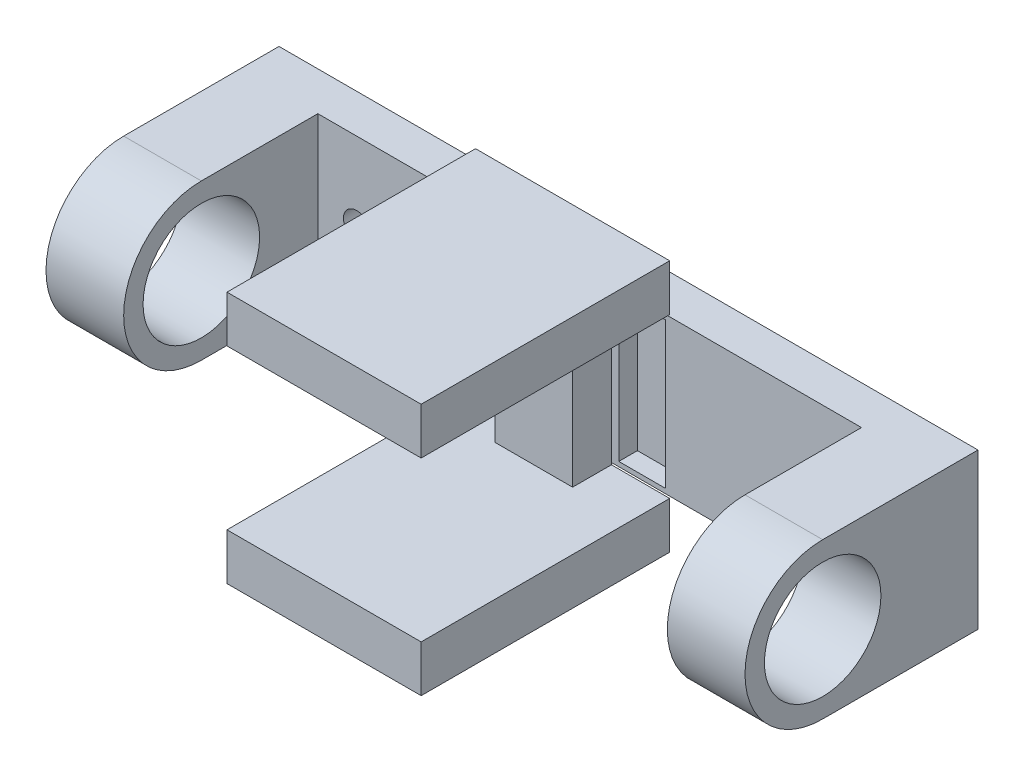
SolidWorks part; units mm, degrees
ref_plane "Plan de face" through (0, 0, 0) normal (0, 0, 1) x (1, 0, 0)
ref_plane "Plan de dessus" through (0, 0, 0) normal (0, 1, 0) x (1, 0, 0)
ref_plane "Plan de droite" through (0, 0, 0) normal (1, 0, 0) x (0, 0, -1)
sketch "Esquisse1" plane through (0, 0, 0) normal (0, 0, 1) x (1, 0, 0)
  line L1 (0, 0) -> (90, 0)
  line L2 (0, 0) -> (0, 20)
  line L3 (0, 20) -> (90, 20)
  line L4 (90, 0) -> (90, 20)
  dimension "D1" = 90
  dimension "D2" = 20
extrude "Boss.-Extru.1" add sketch "Esquisse1" along normal blind 5
sketch "Esquisse2" plane through (0, 0, 5) normal (0, 0, 1) x (1, 0, 0)
  line L0 (90, 20) -> (0, 20) construction
  line L1 (0, 0) -> (10, 0)
  line L2 (0, 0) -> (0, 20)
  line L3 (0, 20) -> (10, 20)
  line L4 (10, 0) -> (10, 20)
  dimension "D1" = 10
extrude "Boss.-Extru.2" add sketch "Esquisse2" along normal blind 30
sketch "Esquisse3" plane through (0, 0, 0) normal (-1, 0, 0) x (0, 0, 1)
  line L0 (0, 20) -> (0, 0) construction
  line L1 (35, 20) -> (0, 20) construction
  line L2 (35, 20) -> (35, 0) construction
  line L3 (35, 0) -> (0, 0) construction
  line L4 (35, 20) -> (20, 20)
  line L5 (35, 20) -> (35, 0)
  line L6 (35, 0) -> (20, 0)
  circle A0 centre (20, 10) radius 7.5
  arc A1 (20, 0) -> (20, 20) centre (20, 10) ccw
  dimension "D2" = 15
  dimension "D4" = 20
  dimension "D1" = 20
  dimension "D3" = 10
extrude "Enlèv. mat.-Extru.1" cut sketch "Esquisse3" against normal up to surface (10 mm away) up to face at (10, 10, 20)
ref_plane "Plan1" through (45, 0, 0) normal (1, 0, 0) x (0, 0, -1)
mirror "Symétrie1" about plane through (45, 0, 0) normal (1, 0, 0) of "Enlèv. mat.-Extru.1", "Boss.-Extru.2"
sketch "Esquisse5" plane through (0, 0, 5) normal (0, 0, 1) x (1, 0, 0)
  line L0 (80, 20) -> (10, 20) construction
  line L1 (48.75, 19.4) -> (54.75, 19.4)
  line L2 (48.75, 19.4) -> (48.75, 0.6)
  line L3 (48.75, 0.6) -> (54.75, 0.6)
  line L4 (54.75, 19.4) -> (54.75, 0.6)
  line L10 (45, -11) -> (45, 11) construction
  point P7 (51.75, 19.4)
  dimension "D1" = 18.8
  dimension "D2" = 6
  dimension "D3" = 0.6
  dimension "D4" = 6.75
extrude "Enlèv. mat.-Extru.2" cut sketch "Esquisse5" against normal offset from surface (2.4 mm away) 2.6 up to face at (45, 10, 0)
sketch "Esquisse6" plane through (0, 0, 5) normal (0, 0, 1) x (1, 0, 0)
  line L0 (80, 20) -> (10, 20) construction
  line L1 (10, 0) -> (10, 20) construction
  line L2 (80, 20) -> (80, 0) construction
  circle A0 centre (25, 10) radius 1.5 construction
  circle A1 centre (68, 10) radius 1.5
  dimension "D1" = 3
  dimension "D4" = 3
  dimension "D2" = 10
  dimension "D3" = 15
  dimension "D5" = 10
  dimension "D6" = 12
extrude "Enlèv. mat.-Extru.3" [suppressed] cut sketch "Esquisse6" against normal up to surface (5 mm away) up to face at (45, 10, 0)
sketch "Esquisse10" plane through (0, 0, 5) normal (0, 0, 1) x (1, 0, 0)
  line L0 (48.75, 19.4) -> (48.75, 0.6) construction
  line L1 (17.35, 13.05) -> (32.35, 13.05)
  line L2 (17.35, 13.05) -> (17.35, 6.95)
  line L3 (17.35, 6.95) -> (32.35, 6.95)
  line L4 (32.35, 13.05) -> (32.35, 6.95)
  line L5 (80, 20) -> (10, 20) construction
  point P6 (32.35, 10)
  dimension "D1" = 16.4
  dimension "D2" = 15
  dimension "D3" = 6.1
  dimension "D4" = 10
extrude "Enlèv. mat.-Extru.4" cut sketch "Esquisse10" against normal up to surface (5 mm away) up to face at (45, 10, 0)
sketch "Esquisse11" plane through (0, 0, 5) normal (0, 0, 1) x (1, 0, 0)
  line L0 (0, 10) -> (91.8744, 10) construction
  line L2 (45, -11) -> (45, 11) construction
  line L4 (0, 20) -> (0, 0)
  line L5 (90, 20) -> (0, 20)
  line L6 (90, 0) -> (90, 20)
  line L7 (0, 0) -> (90, 0)
  line L8 (0, 20) -> (0, 0) construction
  line L9 (90, 20) -> (0, 20) construction
  line L10 (90, 0) -> (90, 20) construction
  line L11 (0, 0) -> (90, 0) construction
  circle A0 centre (15, 10) radius 1
  circle A1 centre (75, 10) radius 1
  dimension "D2" = 2
  dimension "D3" = 2
  dimension "D4" = 30
  dimension "D5" = 30
  dimension "D1" = 0
extrude "Enlèv. mat.-Extru.5" cut sketch "Esquisse11" against normal blind 10
hole_wizard "Dégagement M31" positions "Esquisse12" profile "Esquisse13" hole size "M3" standard "ISO" end condition through all
sketch "Esquisse12" plane through (0, 0, 5) normal (0, 0, 1) x (1, 0, 0)
  point P0 (15, 10)
  point P3 (75, 10)
sketch "Esquisse13" plane through (15, 10, 5) normal (1, 0, 0) x (0, -1, 0)
  line L0 (0, 0) -> (0, 5)
  line L1 (0, 5) -> (1.7, 5)
  line L2 (1.7, 5) -> (1.7, 0)
  line L5 (1.7, 0) -> (0, 0)
  line L11 (0, -6.35) -> (0, 107.95) construction
  dimension "Diamètre du perçage jusqu'au prochain" = 3.4
  dimension "Profondeur du perçage jusqu'au prochain" = 5
sketch "Esquisse14" plane through (0, 0, 5) normal (0, 0, 1) x (1, 0, 0)
  line L0 (10, 0) -> (80, 0) construction
  line L1 (37.8031, 26.2512) -> (47.8031, 26.2512)
  line L2 (37.8031, 26.2512) -> (37.8031, -6.2488)
  line L3 (37.8031, -6.2488) -> (47.8031, -6.2488)
  line L4 (47.8031, 26.2512) -> (47.8031, -6.2488)
  line L6 (45, -11) -> (45, 11) construction
  point P4 (37.8031, 10.0012)
  point P7 (42.8031, 26.2512)
  dimension "D1" = 32.5
  dimension "D2" = 10.0012
  dimension "D3" = 10
  dimension "D4" = 2.1969
extrude "Boss.-Extru.3" add sketch "Esquisse14" along normal blind 5
sketch "Esquisse16" plane through (0, 0, 10) normal (0, 0, 1) x (1, 0, 0)
  line L1 (30.3031, 26.2512) -> (55.3031, 26.2512)
  line L2 (30.3031, 26.2512) -> (30.3031, 20.2512)
  line L3 (30.3031, 20.2512) -> (55.3031, 20.2512)
  line L4 (55.3031, 26.2512) -> (55.3031, 20.2512)
  line L5 (37.8031, -6.2488) -> (47.8031, -6.2488) construction
  line L10 (30.3031, -0.2488) -> (55.3031, -0.2488)
  line L11 (47.8031, 26.2512) -> (37.8031, 26.2512) construction
  line L12 (30.3031, -0.2488) -> (30.3031, -6.2488)
  line L13 (30.3031, -6.2488) -> (55.3031, -6.2488)
  line L14 (55.3031, -0.2488) -> (55.3031, -6.2488)
  point P13 (42.8031, 26.2512)
  point P14 (42.8031, 26.2512)
  point P15 (42.8031, -6.2488)
  point P16 (42.8031, -6.2488)
  dimension "D1" = 20.5
  dimension "D3" = 25
  dimension "D4" = 25
extrude "Boss.-Extru.4" add sketch "Esquisse16" along normal blind 32 from surface starting at face at (42.8031, -3.1244, 5)
equation "\"D3@Esquisse5\"=(20-\"D1@Esquisse5\")/2"
